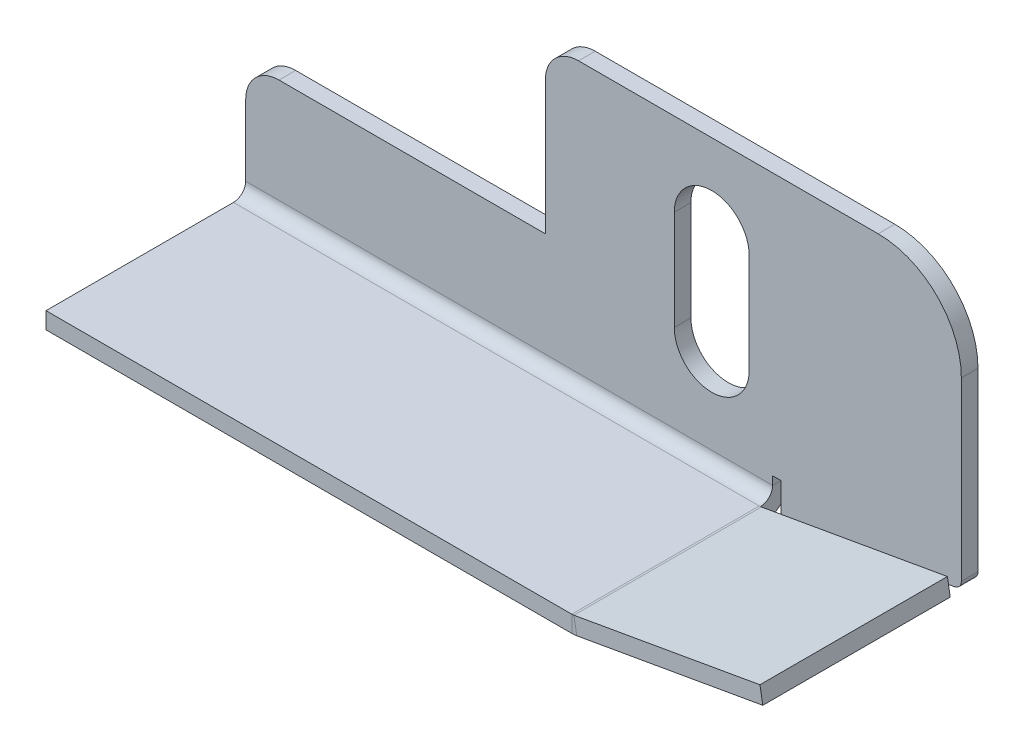
SolidWorks part; units mm, degrees
note: The reader was unsure of these and kept them because the rebuilt part matched: flange length of "Kante-Lasche2", "Kante-Lasche3".
material "1.4301 (X5CrNi18-10)"
ref_plane "Ebene vorne" through (0, 0, 0) normal (0, 0, 1) x (1, 0, 0)
ref_plane "Ebene oben" through (0, 0, 0) normal (0, 1, 0) x (1, 0, 0)
ref_plane "Ebene rechts" through (0, 0, 0) normal (1, 0, 0) x (0, 0, -1)
sketch "Skizze1" plane through (0, 0, 0) normal (0, 0, 1) x (1, 0, 0)
  line L4 (-28.3426, 0.5) -> (-60, 0.5)
  line L9 (-60, 0.5) -> (-60, 6.5)
  line L10 (-32, 7.5) -> (-32, 13.5) construction
  line L11 (-29.75, 7.5) -> (-29.75, 13.5)
  line L12 (-34.25, 7.5) -> (-34.25, 13.5)
  line L13 (-42, 8.5) -> (-58, 8.5)
  line L14 (-17, 2.5) -> (-28.3426, 0.5)
  line L15 (-17, 13.5) -> (-17, 2.5)
  line L16 (-40, 18.5) -> (-22, 18.5)
  line L17 (-42, 8.5) -> (-42, 16.5)
  arc A5 (-29.75, 7.5) -> (-34.25, 7.5) centre (-32, 7.5) cw
  arc A6 (-34.25, 13.5) -> (-29.75, 13.5) centre (-32, 13.5) cw
  arc A7 (-58, 8.5) -> (-60, 6.5) centre (-58, 6.5) ccw
  arc A8 (-42, 16.5) -> (-40, 18.5) centre (-40, 16.5) cw
  arc A9 (-17, 13.5) -> (-22, 18.5) centre (-22, 13.5) ccw
  point P22 (-32, 10.5)
  dimension "D8" = 18
  dimension "D9" = 18
  dimension "D10" = 8
  dimension "D4" = 5
  dimension "D5" = 2
  dimension "D6" = 2
  dimension "D1" = 4.5
  dimension "D2" = 6
  dimension "D3" = 100
  dimension "D7" = 25
  dimension "D11" = 10
  dimension "D12" = 8
  dimension "D13" = 16
  dimension "D14" = 0.5
base flange "Basis-Blech1" sketch "Skizze1" thickness 1 reverse thickness direction yes parameters "D1"=0.7366
edge flange "Kante-Lasche2" sketch "Skizze19" flange angle 90 flange length 13 flange position material inside bend radius 0.7366 thickness 1 relief rectangular parameters "D6"=10
sketch "Skizze19" plane through (0, 0.5, 1) normal (0, -1, 0) x (1, 0, 0)
  line L2 (-60, 0) -> (-60, 12)
  line L3 (-60, 12) -> (-28.3426, 12)
  line L4 (-28.3426, 12) -> (-28.3426, 0)
  line L7 (-60, 0) -> (-28.3426, 0) construction
  line L8 (-60, 0) -> (-28.3426, 0)
bend "Kantenbiegung2" bend radius 0.7366 bend angle 90 parameters "D5"=1
edge flange "Kante-Lasche3" sketch "Skizze24" flange angle 170 flange length 11.5 flange position material outside bend radius 0.7366 thickness 1 relief none parameters "D6"=10
sketch "Skizze24" plane through (-28.3426, 1.5, 0) normal (0.1736, -0.9848, 0) x (0, 0, -1)
  line L2 (-13, 0) -> (-13, 11.4125)
  line L3 (-13, 11.4125) -> (-1.7366, 11.4125)
  line L4 (-1.7366, 11.4125) -> (-1.7366, 0)
  line L7 (-1.7366, 0) -> (-13, 0) construction
  line L8 (-1.7366, 0) -> (-13, 0)
bend "Kantenbiegung3" bend radius 0.7366 bend angle 10 parameters "D5"=2
fillet "Verrundung1" radius 0.5 2 edges at (-27.8426, 0.5882, 0.5) (-17, 2.5, 0.5)
sketch "Biegung-Linien1" [suppressed] plane through (0, 0, 0) normal (0, 1, 0) x (1, 0, 0)
sketch "Rahmen1" [suppressed] plane through (0, 0, 0) normal (0, 1, 0) x (1, 0, 0)
sheet metal parameters "Blech1" thickness 1 parameters "D1"=0.7366
flat pattern "Abwicklung1" [suppressed]
sketch "Biegung-Linien2" plane through (0, 0, 0) normal (0, 1, 0) x (1, 0, 0)
sketch3d "Rahmen2" [suppressed]
  line L0 (2, -6, 0) -> (-41, -6, 0) construction
  line L1 (2, 12, 0) -> (-41, 12, 0) construction
  line L2 (2, -6, 0) -> (2, 12, 0) construction
  line L3 (-41, -6, 0) -> (-41, 12, 0) construction
sheet metal parameters "Blech3" thickness 1 parameters "D1"=0.7366
flat pattern "Abwicklung1"
sketch "Biegung-Linien2" plane through (0, 0, 0) normal (0, 0, -1) x (-1, 0, 0)
  line L0 (28.3426, 1.2654) -> (60, 1.2654) construction
  line L1 (28.3426, 1.2654) -> (60, 1.2654) construction
sketch3d "Rahmen2" [suppressed]
  line L0 (2, 12, 0) -> (-41, 12, 0) construction
  line L1 (2, -17.4692, 0) -> (-41, -17.4692, 0) construction
  line L2 (2, 12, 0) -> (2, -17.4692, 0) construction
  line L3 (-41, 12, 0) -> (-41, -17.4692, 0) construction
bend of the flat pattern "Abwickeln-<Kantenbiegung2>1"
sheet metal parameters "Blech4" thickness 1 parameters "D1"=0.7366
flat pattern "Abwicklung1"
sketch "Biegung-Linien2" plane through (0, 0, 0) normal (0, 0, -1) x (-1, 0, 0)
  line L0 (28.3426, 1.2654) -> (60, 1.2654) construction
  line L1 (28.3426, 1.2654) -> (60, 1.2654) construction
sketch3d "Rahmen2" [suppressed]
  line L0 (2, 12, 0) -> (-41, 12, 0) construction
  line L1 (2, -17.4692, 0) -> (-41, -17.4692, 0) construction
  line L2 (2, 12, 0) -> (2, -17.4692, 0) construction
  line L3 (-41, 12, 0) -> (-41, -17.4692, 0) construction
bend of the flat pattern "Abwickeln-<Kantenbiegung2>1"
bend of the flat pattern "Abwickeln-<Kantenbiegung3>1"
